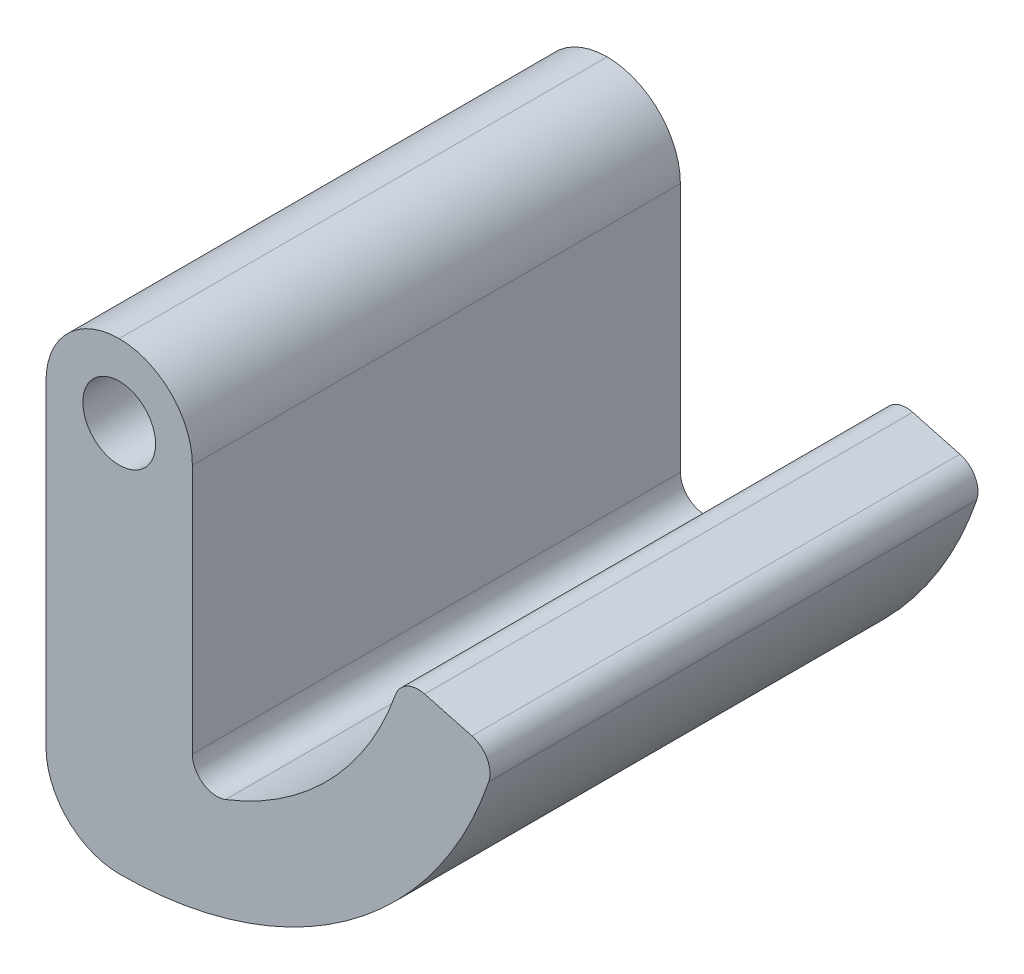
SolidWorks part; units mm, degrees
ref_plane "Front Plane" through (0, 0, 0) normal (0, 0, 1) x (1, 0, 0)
ref_plane "Top Plane" through (0, 0, 0) normal (0, 1, 0) x (1, 0, 0)
ref_plane "Right Plane" through (0, 0, 0) normal (1, 0, 0) x (0, 0, -1)
sketch "Sketch2" plane through (0, 0, 0) normal (0, 0, 1) x (1, 0, 0)
  line L1 (-6, 6) -> (6, 6)
  line L2 (-6, 6) -> (-6, -32)
  line L4 (6, 6) -> (6, -23.2379)
  line L5 (23.1822, -6.2117) -> (30.9096, -8.2822)
  line L6 (0, 0) -> (23.1822, -6.2117) construction
  line L7 (0, -24) -> (0, 0) construction
  line L10 (-6, -32) -> (0, -32)
  line L11 (0, -32) -> (0, -24) construction
  arc A0 (6, -23.2379) -> (23.1822, -6.2117) centre (0, 0) ccw
  arc A1 (0, -32) -> (30.9096, -8.2822) centre (0, 0) ccw
  circle A2 centre (0, 0) radius 2.98
  arc A3 (0, -24) -> (6, -23.2379) centre (0, 0) ccw construction
  dimension "D1" = 6
  dimension "D2" = 5.96
  dimension "D4" = 75
  dimension "D5" = 24
  dimension "D6" = 8
  dimension "D3" = 12
extrude "Boss-Extrude1" add sketch "Sketch2" along normal mid plane 40
fillet "Fillet1" radius 6 3 edges at (6, 6, 0) (-6, 6, 0) (-6, -32, 0)
fillet "Fillet2" radius 2 3 edges at (30.9096, -8.2822, 0) (23.1822, -6.2117, 0) (6, -23.2379, 0)
